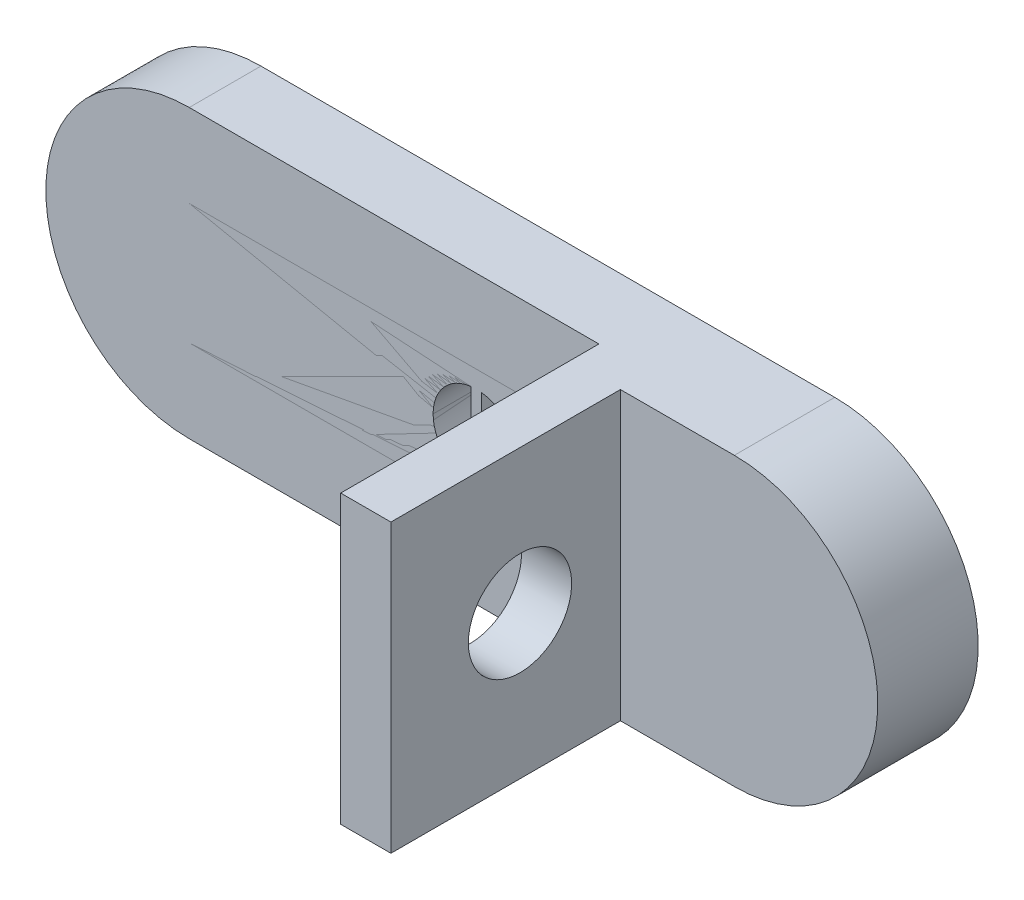
SolidWorks part; units mm, degrees
material "黄铜"
ref_plane "前视基准面" through (0, 0, 0) normal (0, 0, 1) x (1, 0, 0)
ref_plane "上视基准面" through (0, 0, 0) normal (0, 1, 0) x (1, 0, 0)
ref_plane "右视基准面" through (0, 0, 0) normal (1, 0, 0) x (0, 0, -1)
sketch "草图1" plane through (0, 0, 0) normal (0, 0, 1) x (1, 0, 0)
  line L0 (-20, 0) -> (20, 0) construction
  line L1 (-20, 10) -> (20, 10)
  line L2 (-20, -10) -> (20, -10)
  line L3 (20, 0) -> (-20, 0) construction
  line L4 (-0.375, -3) -> (0.375, -3)
  line L5 (-0.375, -3) -> (-0.375, 3)
  line L6 (-0.375, 3) -> (0.375, 3)
  line L7 (0.375, -3) -> (0.375, 3)
  line L8 (-0.375, -3) -> (0.375, 3) construction
  line L9 (-0.375, 3) -> (0.375, -3) construction
  line L10 (20, -4.2094) -> (-20, -4.2094)
  line L11 (20, 4.2094) -> (-20, 4.2094)
  arc A0 (-20, 10) -> (-20, -10) centre (-20, 0) ccw
  arc A1 (20, -10) -> (20, 10) centre (20, 0) ccw
  circle A2 centre (0, 0) radius 3
  arc A3 (20, -4.2094) -> (20, 4.2094) centre (20, 0) ccw
  arc A4 (-20, 4.2094) -> (-20, -4.2094) centre (-20, 0) ccw
  point P2 (0, 0)
  point P16 (0, 0)
  dimension "D1" = 10
  dimension "D3" = 6
  dimension "D2" = 40
  dimension "D4" = 6
  dimension "D5" = 0.75
extrude "凸台-拉伸1" add sketch "草图1" along normal blind 5 contours L2 A1 L1 A0 A2 L5 L6 L7 L4 region at (0, -3.7179, 0)
extrude "凸台-拉伸2" add sketch "草图1<3>" along normal blind 5 contours L5 L6 L7 L4
sketch "草图1<3>" plane through (0, 0, 0) normal (0, 0, 1) x (1, 0, 0) same geometry as "草图1"
extrude "凸台-拉伸10" add sketch "草图1" along normal blind 5 separate body contours L2 A1 L1 A0 A2 L5 L6 L7 L4 region at (0, -3.7179, 0)
extrude "凸台-拉伸16" add sketch "草图1<15>" along normal blind 5 contours L2 A1 L1 A0 A4 L11 A3 L10 region at (0, 9.3675, 0)
sketch "草图1<15>" plane through (0, 0, 0) normal (0, 0, 1) x (1, 0, 0) same geometry as "草图1"
sketch "草图2" plane through (0, 0, 5) normal (0, 0, 1) x (1, 0, 0)
  line L0 (-20, 0) -> (20, 0) construction
  line L1 (8.5581, 10) -> (12.0581, 10)
  line L2 (8.5581, 10) -> (8.5581, -10)
  line L3 (8.5581, -10) -> (12.0581, -10)
  line L4 (12.0581, 10) -> (12.0581, -10)
  line L5 (8.5581, 10) -> (12.0581, -10) construction
  line L6 (8.5581, -10) -> (12.0581, 10) construction
  line L7 (-20, -10) -> (20, -10) construction
  point P0 (10.3081, 0)
  dimension "D1" = 3.5
extrude "凸台-拉伸18" add sketch "草图2" along normal blind 18 and the other way through all
sketch "草图3" plane through (8.5581, 0, 0) normal (-1, 0, 0) x (0, 0, 1)
  line L0 (5, 10) -> (5, -10) construction
  circle A0 centre (14, 0) radius 3.6
  point P2 (5, 0)
  dimension "D1" = 7.2
  dimension "D2" = 9
extrude "切除-拉伸2" cut sketch "草图3" against normal blind 3.5
sketch "草图4" plane through (0, 0, 5) normal (0, 0, 1) x (1, 0, 0)
  line L1 (20, 10) -> (12.0581, 10)
  line L2 (20, 10) -> (20, -10)
  line L3 (20, -10) -> (12.0581, -10)
  line L4 (12.0581, 10) -> (12.0581, -10)
  circle A0 centre (20, 0) radius 10
  arc M3 (20, -10) -> (20, 10) centre (20, 0) ccw
extrude "凸台-拉伸21" add sketch "草图4" along normal blind 2 contours L2 M3 | L4 L3 L2 L1 region at (24.2441, 0, 5)
extrude "凸台-拉伸23" add sketch "草图1<20>" along normal blind 5 contours L5 L6 L7 L4
sketch "草图1<20>" plane through (0, 0, 0) normal (0, 0, 1) x (1, 0, 0) same geometry as "草图1"
